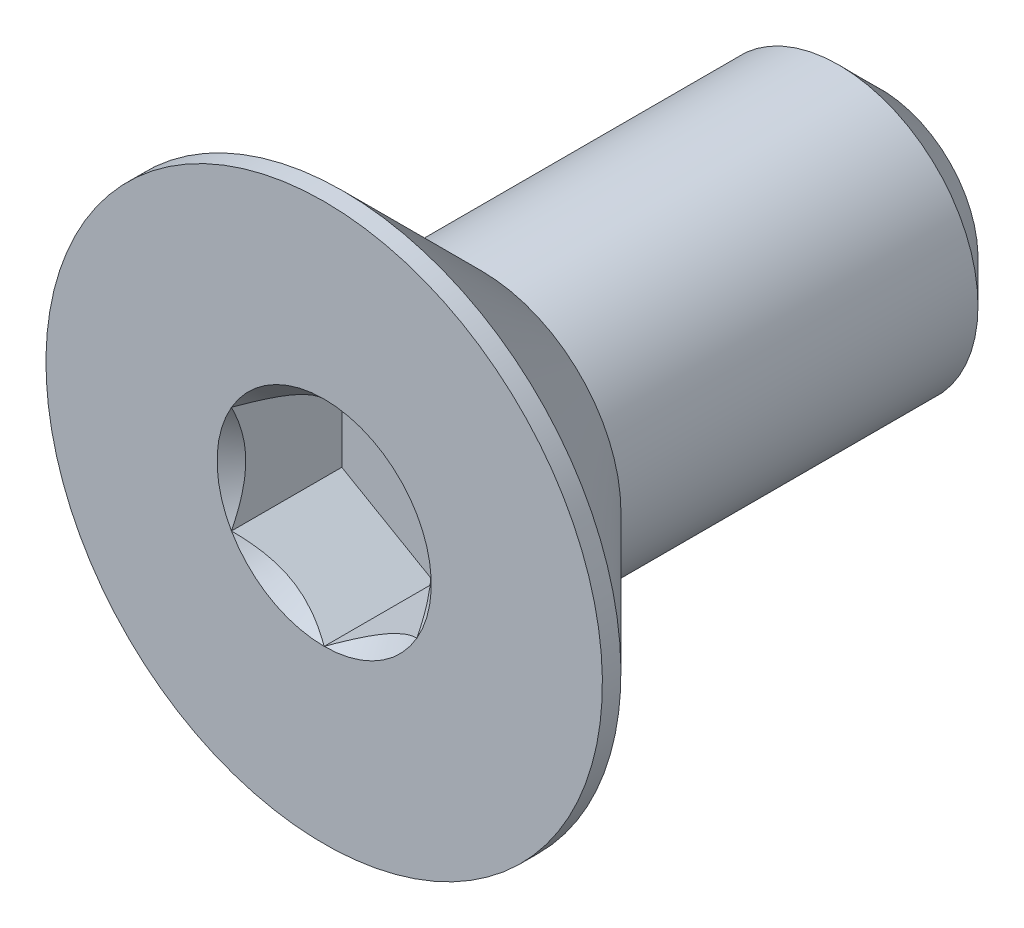
SolidWorks part; units mm, degrees
material "Alloy Steel"
ref_plane "Front" through (0, 0, 0) normal (0, 0, 1) x (1, 0, 0)
ref_plane "Top" through (0, 0, 0) normal (0, 1, 0) x (1, 0, 0)
ref_plane "Right" through (0, 0, 0) normal (1, 0, 0) x (0, 0, -1)
sketch "Sketch1" plane through (0, 0, 0) normal (1, 0, 0) x (0, 0, -1)
  line L0 (-3, 3) -> (-2.8, 3) construction
  line L1 (-2.8, 3) -> (-1.3, 1.5) construction
  line L2 (-3, 1.5) -> (3, 1.5) construction
  line L3 (3, 1.5) -> (3, 0) construction
  line L4 (3, 0) -> (-3, 0) construction
  line L5 (-3, 0) -> (-3, 3) construction
  line L6 (-3, 3) -> (-3, -3) construction
  line L7 (3, 1.5) -> (3, -1.5) construction
  line L8 (-3, -3) -> (-2.8, -3) construction
  line L9 (-2.8, -3) -> (-1.3, -1.5) construction
  line L11 (-3, 1.5) -> (-3, 0) construction
  line L12 (-1.3, 1.5) -> (-1.3, 0) construction
  line L13 (2.9687, 1.5541) -> (3.2188, 1.1211) construction
  line L14 (3.2188, 1.1211) -> (3.4687, 1.5541) construction
  line L15 (3.4687, 1.5541) -> (2.9687, 1.5541) construction
  line L16 (3.2188, 1.5541) -> (3.2188, 1.5) construction
  line L17 (3.2188, 1.5) -> (3.2188, 1.1752) construction
  line L18 (3.2188, 1.1752) -> (3.2188, 1.1211) construction
  line L19 (3.2188, 1.5271) -> (3.4531, 1.5271) construction
  line L20 (3.2188, 1.5271) -> (2.9844, 1.5271) construction
  line L21 (3, 1.5) -> (3.4375, 1.5) construction
  line L22 (3.1875, 1.1752) -> (3.25, 1.1752) construction
  line L23 (3, -1.5) -> (-1.3, -1.5) construction
  point P10 (1.75, -1.5)
  point P24 (-1.3, 1.5)
  point P30 (0, 0)
  dimension "Head Diameter" = 6
  dimension "Head Height" = 1.7
  dimension "Length" = 6
  dimension "Countersink Angle" = 90
  dimension "Thread Pitch" = 0.5
  dimension "D2" = 0.0625
  dimension "Minimum Thread Length" = 4.3
  dimension "Thread Size" = 3
  dimension "D1" = 1.25
sketch "Sketch2" plane through (0, 0, 0) normal (0, 0, 1) x (1, 0, 0)
  line L1 (0, 1.1547) -> (-1, 0.5774) construction
  line L2 (-1, 0.5774) -> (-1, -0.5774) construction
  line L3 (-1, -0.5774) -> (0, -1.1547) construction
  line L4 (0, -1.1547) -> (1, -0.5774) construction
  line L5 (1, -0.5774) -> (1, 0.5774) construction
  line L6 (1, 0.5774) -> (0, 1.1547) construction
  circle A0 centre (0, 0) radius 1 construction
  dimension "Drive Size" = 2
sketch "Sketch3" plane through (0, 0, 0) normal (1, 0, 0) x (0, 0, -1)
  line L0 (-3, 1.5) -> (3, 1.5)
  line L1 (3, 1.5) -> (3, 0)
  line L2 (3, 0) -> (-3, 0)
  line L3 (-3, 0) -> (-3, 1.5)
revolve "Revolve1" add sketch "Sketch3" angle 360 about L4
chamfer "Chamfer1" distance 0.45 angle 45 1 edges at (0, 1.5, -3)
sketch "Sketch6" plane through (0, 0, 0) normal (1, 0, 0) x (0, 0, -1)
  line L0 (-3, 3) -> (-2.8, 3)
  line L1 (-2.8, 3) -> (-1.3, 1.5)
  line L2 (-1.3, 1.5) -> (-1.3, 0)
  line L3 (-1.3, 0) -> (-3, 0)
  line L4 (-3, 0) -> (-3, 3)
revolve "Revolve2" add sketch "Sketch6" angle 360 about L4
sketch "Sketch8" plane through (0, 0, 3) normal (0, 0, 1) x (1, 0, 0)
  line L0 (0, 1.1547) -> (-1, 0.5774) construction
  line L1 (1, 0.5774) -> (0, 1.1547) construction
  line L2 (1, -0.5774) -> (1, 0.5774) construction
  line L3 (0, -1.1547) -> (1, -0.5774) construction
  line L4 (-1, 0.5774) -> (-1, -0.5774) construction
  line L5 (-1, -0.5774) -> (0, -1.1547) construction
  line L6 (0, 1.1547) -> (-1, 0.5774)
  line L7 (1, 0.5774) -> (0, 1.1547)
  line L8 (1, -0.5774) -> (1, 0.5774)
  line L9 (0, -1.1547) -> (1, -0.5774)
  line L10 (-1, 0.5774) -> (-1, -0.5774)
  line L11 (-1, -0.5774) -> (0, -1.1547)
extrude "Cut-Extrude1" cut sketch "Sketch8" against normal blind 1.19
sketch "Sketch9" plane through (0, 0, 3) normal (0, 0, 1) x (1, 0, 0)
  circle A0 centre (0, 0) radius 1.1547
extrude "Cut-Extrude2" cut sketch "Sketch9" against normal up to next (1.19 mm away) draft 45
ref_plane "Plane1" [suppressed] through (0, 0, 1.3) normal (0, 0, 1) x (1, 0, 0)
split "Split1" [suppressed] bodies to split 124
sketch "Sketch4" [suppressed] plane through (0, 0, -3) normal (0, 0, -1) x (-1, 0, 0)
  circle A0 centre (0, 0) radius 1.5 construction
  circle A1 centre (0, 0) radius 1.5
curve "Helix/Spiral1" [suppressed] pitch 0.5 height 4.8 turns 9.6
sketch "Sketch10" [suppressed] plane through (0, 0, 0) normal (1, 0, 0) x (0, 0, -1)
  line L0 (2.9844, 1.5271) -> (3.4531, 1.5271)
  line L1 (3.4531, 1.5271) -> (3.25, 1.1752)
  line L2 (3.25, 1.1752) -> (3.1875, 1.1752)
  line L3 (3.1875, 1.1752) -> (2.9844, 1.5271)
sweep "Cut-Sweep1" [suppressed] cut profiles "Sketch10" path "Helix/Spiral1"
equation "\"D2@Sketch1\" = \"Thread Pitch@Sketch1\" / 8"
equation "\"D4@Helix/Spiral1\"=\"Thread Pitch@Sketch1\""
equation "\"D3@Helix/Spiral1\"=\"Minimum Thread Length@Sketch1\"+\"Thread Pitch@Sketch1\""
equation "\"D1@Chamfer1\"=\"Thread Size@Sketch1\"*.15"
equation "\"D1@Cut-Extrude1\"=\"Head Height@Sketch1\"*.7"
equation "\"D1@Sketch1\"=\"Thread Pitch@Sketch1\"*2.5"
